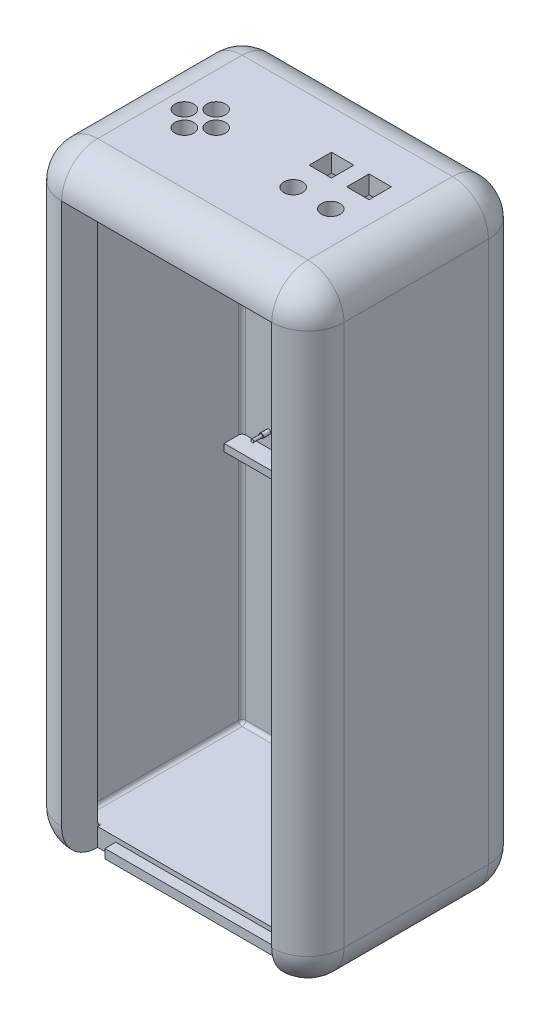
SolidWorks part; units mm, degrees
ref_plane "Front Plane" through (0, 0, 0) normal (0, 0, 1) x (1, 0, 0)
ref_plane "Top Plane" through (0, 0, 0) normal (0, 1, 0) x (1, 0, 0)
ref_plane "Right Plane" through (0, 0, 0) normal (1, 0, 0) x (0, 0, -1)
sketch "Sketch1" plane through (0, 0, 0) normal (0, 0, 1) x (1, 0, 0)
  line L1 (10, 0) -> (68.2, 0)
  line L2 (0, 10) -> (0, 160)
  line L3 (10, 170) -> (68.2, 170)
  line L4 (78.2, 10) -> (78.2, 160)
  arc A0 (68.2, 0) -> (78.2, 10) centre (68.2, 10) ccw
  arc A1 (10, 0) -> (0, 10) centre (10, 10) cw
  arc A2 (68.2, 170) -> (78.2, 160) centre (68.2, 160) cw
  arc A3 (0, 160) -> (10, 170) centre (10, 160) cw
  point P9 (0, 0)
  dimension "D1" = 10
  dimension "D3" = 150
  dimension "D2" = 78.2
extrude "Boss-Extrude1" add sketch "Sketch1" along normal blind 50 contours L2 A3 L3 A2 L4 A0 L1 A1
sketch "Sketch3" plane through (0, 0, 50) normal (0, 0, 1) x (1, 0, 0)
  line L13 (10, 170) -> (68.2, 170) construction
  line L14 (5, 165) -> (73.2, 165)
  line L15 (5, 165) -> (5, 5)
  line L16 (5, 5) -> (73.2, 5)
  line L17 (73.2, 165) -> (73.2, 5)
  line L18 (0, 10) -> (0, 160) construction
  line L19 (78.2, 10) -> (78.2, 160) construction
  line L20 (10, 0) -> (68.2, 0) construction
  dimension "D1" = 5
  dimension "D2" = 5
  dimension "D3" = 5
  dimension "D4" = 5
extrude "Cut-Extrude3" cut sketch "Sketch3" against normal blind 45
sketch "Sketch6" plane through (0, 0, 5) normal (0, 0, 1) x (1, 0, 0)
  line L0 (5, 165) -> (5, 5) construction
  line L1 (5, 72.4) -> (68.8196, 72.4)
  line L2 (5, 72.4) -> (5, 74.4)
  line L3 (5, 74.4) -> (68.8196, 74.4)
  line L4 (68.8196, 72.4) -> (68.8196, 74.4)
  line L5 (5, 5) -> (73.2, 5) construction
  dimension "D1" = 67.4
  dimension "D2" = 2
extrude "Boss-Extrude3" add sketch "Sketch6" along normal blind 5
sketch "Sketch8" plane through (0, 0, 5) normal (0, 0, 1) x (1, 0, 0)
  line L0 (73.2, 5) -> (73.2, 165) construction
  line L1 (68.8196, 74.4) -> (5, 74.4) construction
  circle A0 centre (48.22, 91.4) radius 1.5
  dimension "D2" = 3
  dimension "D1" = 24.98
  dimension "D3" = 17
extrude "Boss-Extrude4" add sketch "Sketch8" along normal blind 2
sketch "Sketch10" plane through (0, 0, 7) normal (0, 0, 1) x (1, 0, 0)
  circle A0 centre (48.22, 91.4) radius 1.15
  dimension "D1" = 2.3
extrude "Boss-Extrude5" add sketch "Sketch10" along normal blind 2.5
sketch "Sketch11" plane through (0, 0, 5) normal (0, 0, 1) x (1, 0, 0)
  line L0 (73.2, 5) -> (73.2, 165) construction
  circle A0 centre (48.22, 76.9) radius 1.5
  circle A1 centre (48.22, 91.4) radius 1.5 construction
  dimension "D1" = 14.5
  dimension "D2" = 24.98
  dimension "D3" = 3
extrude "Boss-Extrude6" add sketch "Sketch11" along normal blind 2
sketch "Sketch12" plane through (0, 0, 7) normal (0, 0, 1) x (1, 0, 0)
  circle A0 centre (48.22, 76.9) radius 1.15
  circle A1 centre (48.22, 76.9) radius 1.5 construction
  dimension "D1" = 2.3
extrude "Boss-Extrude7" add sketch "Sketch12" along normal blind 2.5
sketch "Sketch14" plane through (0, 0, 5) normal (0, 0, 1) x (1, 0, 0)
  line L0 (68.8196, 74.4) -> (5, 74.4) construction
  line L1 (62.2346, 74.4) -> (64.2346, 74.4)
  line L2 (62.2346, 74.4) -> (62.2346, 95.6)
  line L4 (64.2346, 74.4) -> (64.2346, 93.6)
  line L5 (73.2, 5) -> (73.2, 165) construction
  line L6 (62.2346, 95.6) -> (38.8346, 95.6)
  line L7 (64.2346, 93.6) -> (64.2346, 95.6)
  line L11 (38.8346, 95.6) -> (38.8346, 115)
  line L16 (38.8346, 115) -> (64.2346, 115)
  line L20 (42.8346, 99.6) -> (64.2346, 99.6)
  line L21 (64.2346, 95.6) -> (64.2346, 99.6)
  line L25 (42.8346, 111) -> (42.8346, 99.6)
  line L28 (42.8346, 111) -> (62.2346, 111)
  line L31 (64.2346, 115) -> (64.2346, 107)
  line L32 (64.2346, 107) -> (62.2346, 107)
  line L33 (62.2346, 111) -> (62.2346, 107)
  line L34 (68.8196, 74.4) -> (5, 74.4) construction
  dimension "D1" = 19.2
  dimension "D2" = 21.2
  dimension "D3" = 11.4
  dimension "D4" = 8.9654
  dimension "D5" = 4
  dimension "D6" = 4
  dimension "D10" = 4
  dimension "D11" = 2
  dimension "D12" = 4
extrude "Boss-Extrude8" add sketch "Sketch14" along normal blind 2
sketch "Sketch18" plane through (0, 0, 7) normal (0, 0, 1) x (1, 0, 0)
  line L0 (64.2346, 74.4) -> (64.2346, 99.6) construction
  line L1 (62.2346, 74.4) -> (64.2346, 74.4)
  line L2 (62.2346, 74.4) -> (62.2346, 76.2)
  line L3 (62.2346, 76.2) -> (64.2346, 76.2)
  line L4 (64.2346, 74.4) -> (64.2346, 76.2)
  line L5 (64.2346, 74.4) -> (64.2346, 99.6) construction
  line L6 (62.2346, 95.6) -> (64.2346, 95.6)
  line L7 (62.2346, 95.6) -> (62.2346, 91.8)
  line L8 (62.2346, 91.8) -> (64.2346, 91.8)
  line L9 (64.2346, 95.6) -> (64.2346, 91.8)
  dimension "D1" = 1.8
  dimension "D2" = 3.8
extrude "Boss-Extrude12" add sketch "Sketch18" along normal blind 3
sketch "Sketch22" plane through (0, 0, 7) normal (0, 0, 1) x (1, 0, 0)
  line L0 (64.2346, 95.6) -> (64.2346, 97.6)
  line L1 (64.2346, 74.4) -> (64.2346, 99.6) construction
  line L2 (64.2346, 95.6) -> (64.2346, 99.6) construction
  line L3 (64.2346, 97.6) -> (40.8346, 97.6)
  line L4 (40.8346, 97.6) -> (40.8346, 113)
  line L5 (40.8346, 113) -> (64.2346, 113)
  line L6 (64.2346, 107) -> (64.2346, 115) construction
  line L7 (64.2346, 113) -> (64.2346, 115)
  line L8 (64.2346, 115) -> (38.8346, 115)
  line L9 (38.8346, 115) -> (38.8346, 95.6)
  line L10 (38.8346, 95.6) -> (64.2346, 95.6)
  dimension "D1" = 2
  dimension "D2" = 2
extrude "Boss-Extrude16" add sketch "Sketch22" along normal blind 3
sketch "Sketch23" plane through (0, 0, 5) normal (0, 0, 1) x (1, 0, 0)
  line L0 (62.2346, 74.4) -> (5, 74.4) construction
  line L1 (38.8346, 115) -> (38.8346, 95.6) construction
  circle A0 centre (34.8346, 78.4) radius 0.6
  circle A1 centre (12.3346, 78.4) radius 0.6
  circle A2 centre (12.3346, 129.4) radius 0.6
  circle A3 centre (34.8346, 129.4) radius 0.6
  dimension "D1" = 1.2
  dimension "D4" = 1.2
  dimension "D6" = 1.2
  dimension "D8" = 1.2
  dimension "D2" = 4
  dimension "D3" = 4
  dimension "D5" = 22.5
  dimension "D7" = 51
extrude "Boss-Extrude17" add sketch "Sketch23" along normal blind 2
sketch "Sketch24" plane through (0, 0, 7) normal (0, 0, 1) x (1, 0, 0)
  circle A0 centre (12.3346, 129.4) radius 0.4
  circle A1 centre (34.8346, 129.4) radius 0.4
  circle A2 centre (34.8346, 78.4) radius 0.4
  circle A3 centre (12.3346, 78.4) radius 0.4
  dimension "D1" = 0.8
  dimension "D2" = 0.8
  dimension "D3" = 0.8
  dimension "D4" = 0.8
extrude "Boss-Extrude18" add sketch "Sketch24" along normal blind 2.5
sketch "Sketch25" plane through (0, 170, 0) normal (0, 1, 0) x (1, 0, 0)
  line L0 (10, -50) -> (10, 0) construction
  line L2 (16.8, -32.8079) -> (16.8, -32.8762)
  circle A0 centre (19.4, -26.6) radius 2.6
  circle A1 centre (15, -31) radius 2.6
  circle A2 centre (23.8, -31) radius 2.6
  circle A3 centre (19.4, -35.4) radius 2.6
  dimension "D8" = 5.2
  dimension "D9" = 5.2
  dimension "D10" = 5.2
  dimension "D11" = 5.2
  dimension "D2" = 8.8
  dimension "D3" = 8.8
  dimension "D4" = 4.4
  dimension "D5" = 5
extrude "Cut-Extrude5" cut sketch "Sketch25" against normal up to next contours A1 | A0 | A2 | A3
sketch "Sketch26" plane through (0, 170, 0) normal (0, 1, 0) x (1, 0, 0)
  line L1 (45.6455, -20.9) -> (51.8455, -20.9)
  line L2 (45.6455, -20.9) -> (45.6455, -27.1)
  line L3 (45.6455, -27.1) -> (51.8455, -27.1)
  line L4 (51.8455, -20.9) -> (51.8455, -27.1)
  line L5 (56.0455, -20.9) -> (62.2455, -20.9)
  line L6 (56.0455, -20.9) -> (56.0455, -27.1)
  line L7 (56.0455, -27.1) -> (62.2455, -27.1)
  line L8 (62.2455, -20.9) -> (62.2455, -27.1)
  line L9 (10, -50) -> (68.2, -50) construction
  circle A0 centre (48.7455, -34.6) radius 2.6
  circle A1 centre (59.1455, -34.6) radius 2.6
  point P12 (0, 0)
  point P13 (0, 0)
  point P14 (51.8455, -24)
  dimension "D1" = 5.2
  dimension "D2" = 5.2
  dimension "D3" = 3.1
  dimension "D4" = 7.5
  dimension "D5" = 7.5
  dimension "D6" = 4.2
  dimension "D7" = 6.2
  dimension "D8" = 6.2
  dimension "D9" = 6.2
  dimension "D10" = 6.2
  dimension "D11" = 3.1
  dimension "D12" = 15.4
extrude "Cut-Extrude6" cut sketch "Sketch26" against normal up to next contours L8 L5 L6 L7 | A0 | A1 | L2 L1 L4 L3 region at (59.1455, 170, 24) region at (48.7455, 170, 34.6) region at (59.1455, 170, 34.6)
fillet "Fillet9" radius 10 8 edges at (75.2711, 2.9289, 0) (39.1, 0, 0) (2.9289, 2.9289, 0) (0, 85, 0) (2.9289, 167.0711, 0) (39.1, 170, 0) (75.2711, 167.0711, 0) (78.2, 85, 0)
sketch "Sketch30" plane through (0, 0, 50) normal (0, 0, 1) x (1, 0, 0)
  line L0 (10, 170) -> (68.2, 170)
  line L1 (78.2, 160) -> (78.2, 10)
  line L2 (10, 0) -> (68.2, 0)
  line L3 (0, 10) -> (0, 160)
  arc A0 (0, 160) -> (10, 170) centre (10, 160) cw
  arc A1 (68.2, 170) -> (78.2, 160) centre (68.2, 160) cw
  arc A2 (78.2, 10) -> (68.2, 0) centre (68.2, 10) cw
  arc A3 (0, 10) -> (10, 0) centre (10, 10) ccw
extrude "Boss-Extrude19" add sketch "Sketch30" along normal blind 10
sketch "Sketch31" plane through (0, 0, 60) normal (0, 0, 1) x (1, 0, 0)
  line L1 (10, 0) -> (68.2, 0)
  line L2 (10, 0) -> (10, 160)
  line L3 (10, 160) -> (68.2, 160)
  line L4 (68.2, 0) -> (68.2, 160)
  line L5 (78.2, 10) -> (78.2, 160) construction
  line L6 (68.2, 170) -> (10, 170) construction
  dimension "D1" = 10
  dimension "D2" = 10
extrude "Cut-Extrude7" cut sketch "Sketch31" against normal blind 10
fillet "Fillet11" radius 1 9 edges at (7.5, 5, 50) (5, 5, 27.5) (5, 85, 50) (5, 165, 27.5) (39.1, 165, 50) (73.2, 165, 27.5) (73.2, 5, 27.5) (70.7, 5, 50) (73.2, 85, 50)
fillet "Fillet12" radius 1 9 edges at (5, 39.2, 5) (5.2929, 5.2929, 5) (5, 119.2, 5) (5.2929, 164.7071, 5) (39.1, 165, 5) (72.9071, 164.7071, 5) (73.2, 85, 5) (72.9071, 5.2929, 5) (39.1, 5, 5)
fillet "Fillet13" radius 10 7 edges at (75.2711, 2.9289, 60) (2.9289, 2.9289, 60) (0, 85, 60) (2.9289, 167.0711, 60) (39.1, 170, 60) (75.2711, 167.0711, 60) (78.2, 85, 60)
sketch "Sketch32" plane through (0, 160, 0) normal (0, -1, 0) x (1, 0, 0)
  line L0 (68.2, 60) -> (10, 60) construction
  line L1 (15, 56.5) -> (63.2, 56.5)
  line L2 (15, 56.5) -> (15, 53.5)
  line L3 (15, 53.5) -> (63.2, 53.5)
  line L4 (63.2, 56.5) -> (63.2, 53.5)
  line L5 (68.2, 50) -> (68.2, 60) construction
  line L8 (10, 50) -> (10, 60) construction
  dimension "D1" = 3
  dimension "D2" = 3.5
  dimension "D3" = 5
  dimension "D4" = 5
extrude "Boss-Extrude20" add sketch "Sketch32" along normal blind 3
sketch "Sketch33" plane through (0, 0, 50) normal (0, 0, 1) x (1, 0, 0)
  line L0 (10, 5) -> (68.2, 5) construction
  line L1 (15, 3.75) -> (63.2, 3.75)
  line L2 (15, 3.75) -> (15, 1.25)
  line L3 (15, 1.25) -> (63.2, 1.25)
  line L4 (63.2, 3.75) -> (63.2, 1.25)
  line L5 (10, 5) -> (10, 0) construction
  line L6 (68.2, 0) -> (68.2, 5) construction
  dimension "D1" = 2.5
  dimension "D2" = 1.25
  dimension "D3" = 5
  dimension "D4" = 5
extrude "Boss-Extrude21" add sketch "Sketch33" along normal blind 3
